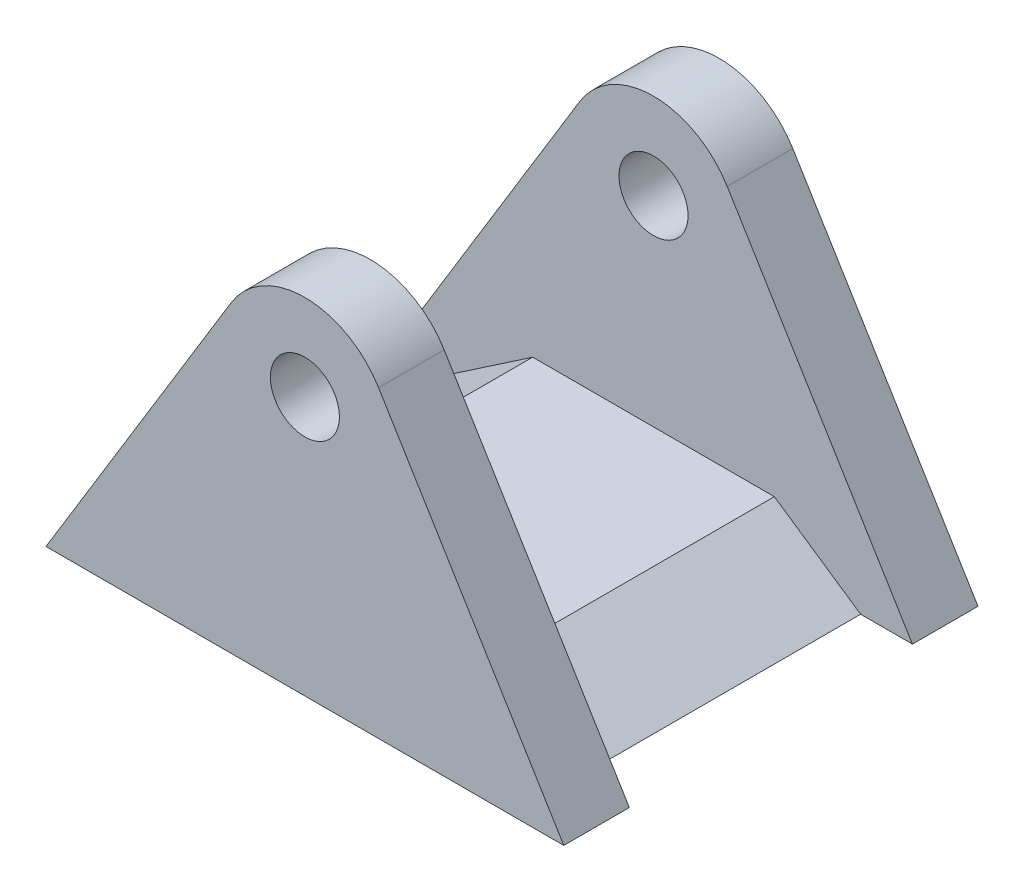
SolidWorks part; units mm, degrees
ref_plane "前视基准面" through (0, 0, 0) normal (0, 0, 1) x (1, 0, 0)
ref_plane "上视基准面" through (0, 0, 0) normal (0, 1, 0) x (1, 0, 0)
ref_plane "右视基准面" through (0, 0, 0) normal (1, 0, 0) x (0, 0, -1)
sketch "草图1" plane through (0, 0, 0) normal (0, 0, 1) x (1, 0, 0)
  line L0 (0, 0) -> (0, 1.7) construction
  line L1 (-6, 0) -> (6, 0)
  line L2 (-3.5, 1.7) -> (3.5, 1.7)
  line L3 (3.5, 1.7) -> (6, 0)
  line L4 (-3.5, 1.7) -> (-6, 0)
  dimension "D1" = 1.7
  dimension "D2" = 6
  dimension "D3" = 3.5
extrude "凸台-拉伸1" add sketch "草图1" along normal blind 4.1 and the other way blind 4.1
sketch "草图2" plane through (0, 0, 4.1) normal (0, 0, 1) x (1, 0, 0)
  line L0 (0, 0) -> (-7.5, 0)
  line L1 (0, 0) -> (0, 6.5) construction
  line L2 (0, 6.5) -> (0, 7.5) construction
  line L3 (0, 7.5) -> (0, 8.5) construction
  line L4 (0, 8.5) -> (0, 10) construction
  line L5 (-7.5, 0) -> (-2.1346, 8.8013)
  line L6 (0, 0) -> (7.5, 0)
  line L7 (7.5, 0) -> (2.1346, 8.8013)
  circle A0 centre (0, 7.5) radius 1
  arc A1 (2.1346, 8.8013) -> (-2.1346, 8.8013) centre (0, 7.5) ccw
  dimension "D1" = 6.5
  dimension "D2" = 1
  dimension "D3" = 1
  dimension "D4" = 1.5
  dimension "D5" = 7.5
  dimension "D6" = 7.5
extrude "凸台-拉伸2" add sketch "草图2" along normal blind 1.9
mirror "镜向1" about plane through (0, 0, 0) normal (0, 0, 1) of "凸台-拉伸2"
sketch "草图3" plane through (0, 0, 0) normal (0, 0, 1) x (1, 0, 0)
  line L0 (0, 0) -> (0, -2) construction
  line L1 (0, -2) -> (0, -2.5) construction
  line L2 (1.5, 0) -> (-1.5, 0)
  line L3 (-7.5, 0) -> (7.5, 0) construction
  line L4 (-1.5, 0) -> (-1.5, -0.6771)
  line L5 (1.95, -2.5) -> (-1.95, -2.5)
  line L6 (-1.95, -2.5) -> (-1.95, -1.5556)
  line L7 (1.95, -2.5) -> (1.95, -1.5556)
  line L8 (1.5, 0) -> (1.5, -0.6771)
  arc A0 (-1.5, -0.6771) -> (-1.95, -1.5556) centre (0, -2) ccw
  arc A1 (1.5, -0.6771) -> (1.95, -1.5556) centre (0, -2) cw
  dimension "D1" = 2
  dimension "D2" = 0.5
  dimension "D3" = 1.5
  dimension "D4" = 1.95
extrude "凸台-拉伸3" add sketch "草图3" along normal blind 2 and the other way blind 2
sketch "草图4" plane through (0, 0, 0) normal (1, 0, 0) x (0, 0, -1)
  line L0 (0, 0) -> (0, -2) construction
  line L1 (0, -2) -> (0, -2.5) construction
  line L2 (2, -2.5) -> (-2, -2.5) construction
  line L3 (0, 0) -> (-1.5, 0) construction
  line L4 (4.1, 0) -> (-4.1, 0) construction
  line L5 (-1.5, 0) -> (-1.5, -0.6771)
  line L6 (0, -2.5) -> (-1.95, -2.5) construction
  line L7 (-1.95, -2.5) -> (-1.95, -1.5556)
  line L8 (-1.95, -2.5) -> (-2, -2.5)
  line L9 (-2, -2.5) -> (-2, 0)
  line L10 (-2, 0) -> (-1.5, 0)
  line L11 (2, 0) -> (1.5, 0)
  line L12 (1.5, 0) -> (1.5, -0.6771)
  line L13 (2, -2.5) -> (2, 0)
  line L14 (1.95, -2.5) -> (1.95, -1.5556)
  line L15 (1.95, -2.5) -> (2, -2.5)
  arc A0 (-1.5, -0.6771) -> (-1.95, -1.5556) centre (0, -2) ccw
  arc A1 (1.5, -0.6771) -> (1.95, -1.5556) centre (0, -2) cw
  dimension "D1" = 2
  dimension "D2" = 1.5
  dimension "D3" = 1.95
extrude "切除-拉伸1" cut sketch "草图4" against normal blind 2 and the other way blind 2
fillet "圆角1" radius 0.1 4 edges at (0, -2.5, -1.95) (-1.95, -2.5, 0) (0, -2.5, 1.95) (1.95, -2.5, 0)
